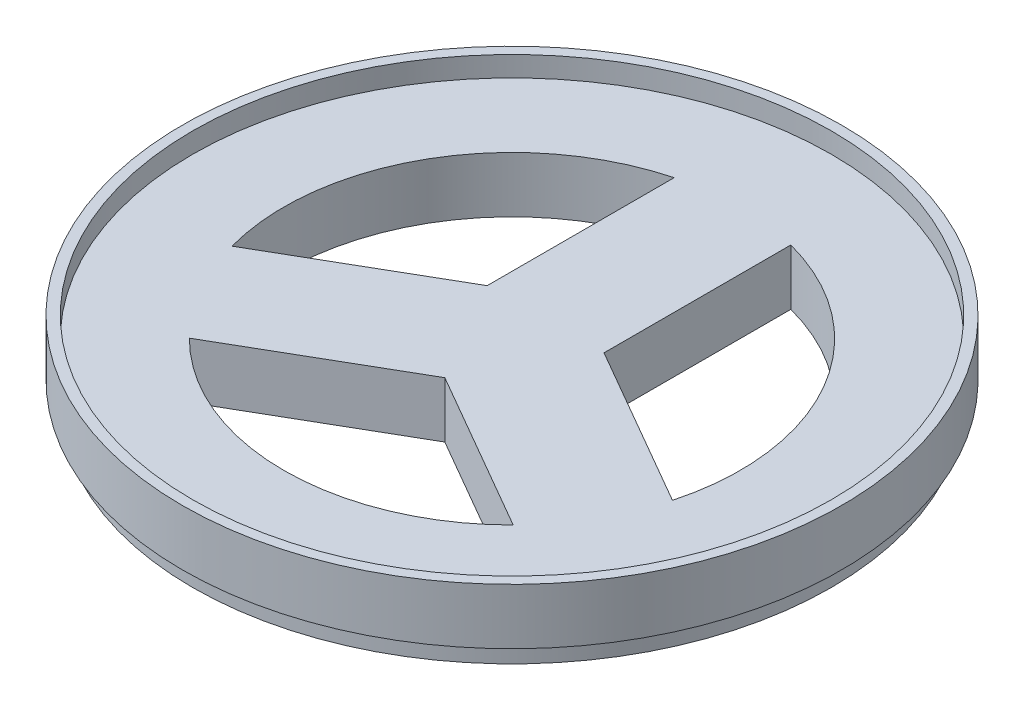
SolidWorks part; units mm, degrees
material "HYPALON"
ref_plane "Front Plane" through (0, 0, 0) normal (0, 0, 1) x (1, 0, 0)
ref_plane "Top Plane" through (0, 0, 0) normal (0, 1, 0) x (1, 0, 0)
ref_plane "Right Plane" through (0, 0, 0) normal (1, 0, 0) x (0, 0, -1)
sketch "Szkic1" plane through (0, 0, 0) normal (0, 1, 0) x (1, 0, 0)
  line L5 (0.0278, -13.2791) -> (31.9372, -31.702)
  line L6 (-11.5139, 6.6155) -> (-11.5139, 43.5021)
  line L7 (11.4861, 6.6636) -> (11.4861, 43.5094)
  line L8 (11.4861, 6.6636) -> (43.4308, -11.7797)
  line L9 (-11.5139, 6.6155) -> (-43.4233, -11.8074)
  line L10 (0.0278, -13.2791) -> (-31.917, -31.7224)
  circle A0 centre (0, 0) radius 65
  circle A1 centre (0, 0) radius 45
  point P22 (0, 0)
  dimension "D1" = 130
  dimension "D2" = 90
  dimension "D5" = 120
  dimension "D3" = 23
  dimension "D7" = 120
  dimension "D8" = 120
  dimension "D6" = 3
sketch "Szkic2" plane through (0, 0, 0) normal (0, 1, 0) x (1, 0, 0)
  circle A0 centre (0, 0) radius 35
  circle A1 centre (0, 0) radius 64
  dimension "D1" = 128
  dimension "D2" = 70
extrude "Dodanie-wyciągnięcie1" add sketch "Szkic1" along normal blind 11 contours L5 A1 L8 L7 L6 L9 L10 | A0 A1 region at (0, 0, 0) region at (-63.1615, 0, 0)
sketch "Szkic3" plane through (0, 11, 0) normal (0, 1, 0) x (1, 0, 0)
  circle A0 centre (0, 0) radius 65
  circle A1 centre (0, 0) radius 63
  circle A2 centre (0, 0) radius 65 construction
  dimension "D1" = 2
extrude "Dodanie-wyciągnięcie2" add sketch "Szkic3" along normal blind 4 contours A0 | A1
sketch "Szkic6" plane through (0, 0, 0) normal (0, -1, 0) x (1, 0, 0)
  circle A0 centre (0, 0) radius 65
  circle A1 centre (0, 0) radius 63
  dimension "D1" = 2
  dimension "D2" = 130
extrude "Wytnij-wyciągnięcie1" cut sketch "Szkic6" against normal blind 4
